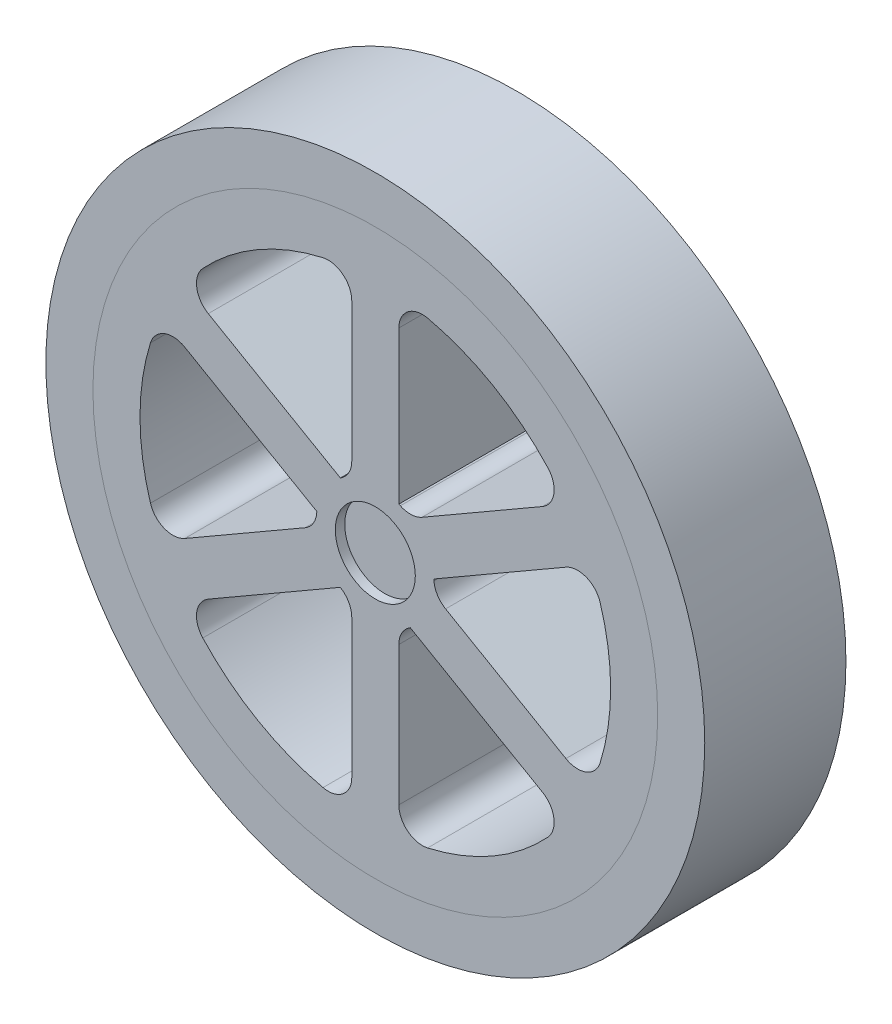
SolidWorks part; units mm, degrees
material "ABS"
ref_plane "正面" through (0, 0, 0) normal (0, 0, 1) x (1, 0, 0)
ref_plane "平面" through (0, 0, 0) normal (0, 1, 0) x (1, 0, 0)
ref_plane "右側面" through (0, 0, 0) normal (1, 0, 0) x (0, 0, -1)
sketch "ｽｹｯﾁ1" plane through (0, 0, 0) normal (0, 0, 1) x (1, 0, 0)
  line L0 (-5, 43.8748) -> (-5, 14.3614)
  line L1 (-5, -14.3614) -> (-5, -43.8748)
  line L2 (0, -12.5) -> (0, 12.5) construction
  line L3 (35.4967, 26.2675) -> (9.9373, 11.5108)
  line L4 (-14.9373, -2.8506) -> (-40.4967, -17.6073)
  line L5 (40.4967, -17.6073) -> (14.9373, -2.8506)
  line L6 (-7.4216, 10.0583) -> (-35.4967, 26.2675)
  line L7 (5, -43.8748) -> (5, -14.3614)
  line L8 (5, 11.4564) -> (5, 43.8748)
  line L9 (-35.4967, -26.2675) -> (-7.4216, -10.0583)
  line L10 (12.4216, 1.3981) -> (40.4967, 17.6073)
  line L11 (-40.4967, 17.6073) -> (-12.4216, 1.3981)
  line L12 (7.4216, -10.0583) -> (35.4967, -26.2675)
  circle A0 centre (0, 0) radius 60
  arc A1 (-12.4216, 1.3981) -> (-12.4552, 1.0568) centre (0, 0) ccw
  arc A2 (-47.7741, 14.7524) -> (-47.7741, -14.7524) centre (0, 0) ccw
  arc A3 (-7.4216, -10.0583) -> (-7.1429, -10.2581) centre (0, 0) ccw
  arc A4 (7.1429, -10.2581) -> (7.4216, -10.0583) centre (0, 0) ccw
  arc A5 (12.4552, 1.0568) -> (12.4216, 1.3981) centre (0, 0) ccw
  arc A6 (5.3124, 11.315) -> (5, 11.4564) centre (0, 0) ccw
  arc A7 (-7.1429, 10.2581) -> (-7.4216, 10.0583) centre (0, 0) ccw
  arc A8 (-36.663, -33.9974) -> (-11.1111, -48.7498) centre (0, 0) ccw
  arc A9 (11.1111, -48.7498) -> (36.663, -33.9974) centre (0, 0) ccw
  arc A10 (47.7741, -14.7524) -> (47.7741, 14.7524) centre (0, 0) ccw
  arc A11 (36.663, 33.9974) -> (11.1111, 48.7498) centre (0, 0) ccw
  arc A12 (-11.1111, 48.7498) -> (-36.663, 33.9974) centre (0, 0) ccw
  arc A13 (35.4967, -26.2675) -> (36.663, -33.9974) centre (32.9967, -30.5977) cw
  arc A14 (-40.4967, 17.6073) -> (-47.7741, 14.7524) centre (-42.9967, 13.2772) ccw
  arc A15 (40.4967, 17.6073) -> (47.7741, 14.7524) centre (42.9967, 13.2772) cw
  arc A16 (-35.4967, -26.2675) -> (-36.663, -33.9974) centre (-32.9967, -30.5977) ccw
  arc A17 (5, 43.8748) -> (11.1111, 48.7498) centre (10, 43.8748) cw
  arc A18 (5, -14.3614) -> (7.1429, -10.2581) centre (10, -14.3614) cw
  arc A19 (5, -43.8748) -> (11.1111, -48.7498) centre (10, -43.8748) ccw
  arc A20 (-35.4967, 26.2675) -> (-36.663, 33.9974) centre (-32.9967, 30.5977) cw
  arc A21 (14.9373, -2.8506) -> (12.4552, 1.0568) centre (17.4373, 1.4796) cw
  arc A22 (40.4967, -17.6073) -> (47.7741, -14.7524) centre (42.9967, -13.2772) ccw
  arc A23 (-40.4967, -17.6073) -> (-47.7741, -14.7524) centre (-42.9967, -13.2772) cw
  arc A24 (-14.9373, -2.8506) -> (-12.4552, 1.0568) centre (-17.4373, 1.4796) ccw
  arc A25 (9.9373, 11.5108) -> (5.3124, 11.315) centre (7.4373, 15.841) cw
  arc A26 (35.4967, 26.2675) -> (36.663, 33.9974) centre (32.9967, 30.5977) ccw
  arc A27 (-5, -43.8748) -> (-11.1111, -48.7498) centre (-10, -43.8748) cw
  arc A28 (-5, -14.3614) -> (-7.1429, -10.2581) centre (-10, -14.3614) ccw
  arc A29 (-5, 14.3614) -> (-7.1429, 10.2581) centre (-10, 14.3614) cw
  arc A30 (-5, 43.8748) -> (-11.1111, 48.7498) centre (-10, 43.8748) ccw
  point P33 (0, 0)
  point P62 (-5, -49.7494)
  point P65 (-5, -11.4564)
  point P68 (-5, 11.4564)
  point P71 (-5, 49.7494)
  dimension "D1" = 120
  dimension "D2" = 25
  dimension "D3" = 100
  dimension "D6" = 5
  dimension "D4" = 10
  dimension "D5" = 6
extrude "ﾎﾞｽ - 押し出し1" add sketch "ｽｹｯﾁ1" along normal blind 30
sketch "ｽｹｯﾁ2" plane through (0, 0, 30) normal (0, 0, 1) x (1, 0, 0)
  circle A0 centre (0, 0) radius 70
  circle A1 centre (0, 0) radius 60 construction
  circle A2 centre (0, 0) radius 60
  dimension "D1" = 10
extrude "ﾎﾞｽ - 押し出し2" add sketch "ｽｹｯﾁ2" against normal up to surface (30 mm away) separate body up to face at (31.354, -0.1, 0)
sketch "ｽｹｯﾁ3" plane through (0, 0, 30) normal (0, 0, 1) x (1, 0, 0)
  circle A0 centre (0, 0) radius 8.5
  dimension "D1" = 17
extrude "ｶｯﾄ - 押し出し1" cut sketch "ｽｹｯﾁ3" against normal blind 2
